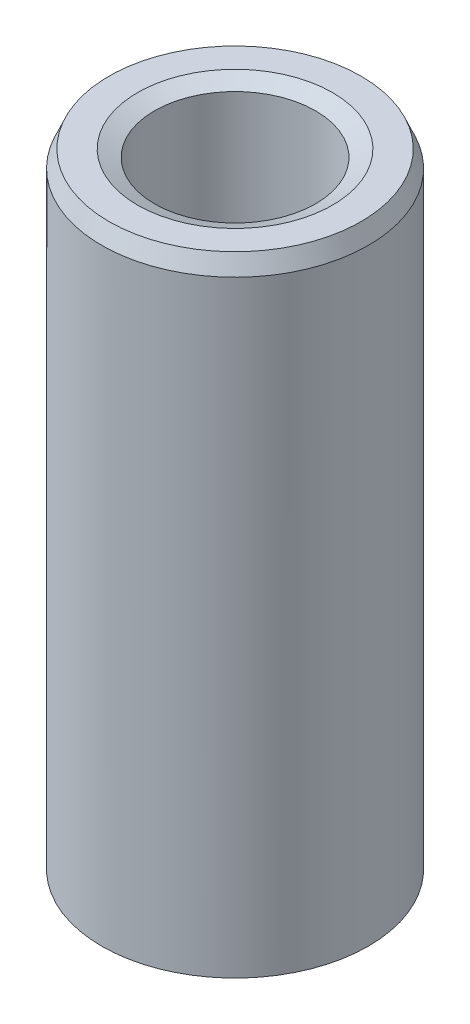
SolidWorks part; units mm, degrees
ref_plane "Front Plane" through (0, 0, 0) normal (0, 0, 1) x (1, 0, 0)
ref_plane "Top Plane" through (0, 0, 0) normal (0, 1, 0) x (1, 0, 0)
ref_plane "Right Plane" through (0, 0, 0) normal (1, 0, 0) x (0, 0, -1)
sketch "Sketch1" plane through (0, 0, 0) normal (0, 1, 0) x (1, 0, 0)
  circle A0 centre (0, 0) radius 22.5
  dimension "SLEEVE_OD" = 45
extrude "Boss-Extrude1" add sketch "Sketch1" along normal blind 106.5189
sketch "Sketch2" plane through (0, 0, 0) normal (0, 1, 0) x (1, 0, 0)
  circle A0 centre (0, 0) radius 13.5979
  dimension "BORE_D" = 27.1958
extrude "Cut-Extrude1" cut sketch "Sketch2" along normal through all
chamfer "Chamfer1" distance 2.8576 angle 23.358 4 edges at (0, 106.5189, 13.5979) (0, 0, 13.5979) (0, 0, 22.5) (0, 106.5189, 22.5) first distance on face at (0, 106.5189, 13.5979) first distance on face at (0, 0, 13.5979) first distance on face at (0, 106.5189, 22.5)
